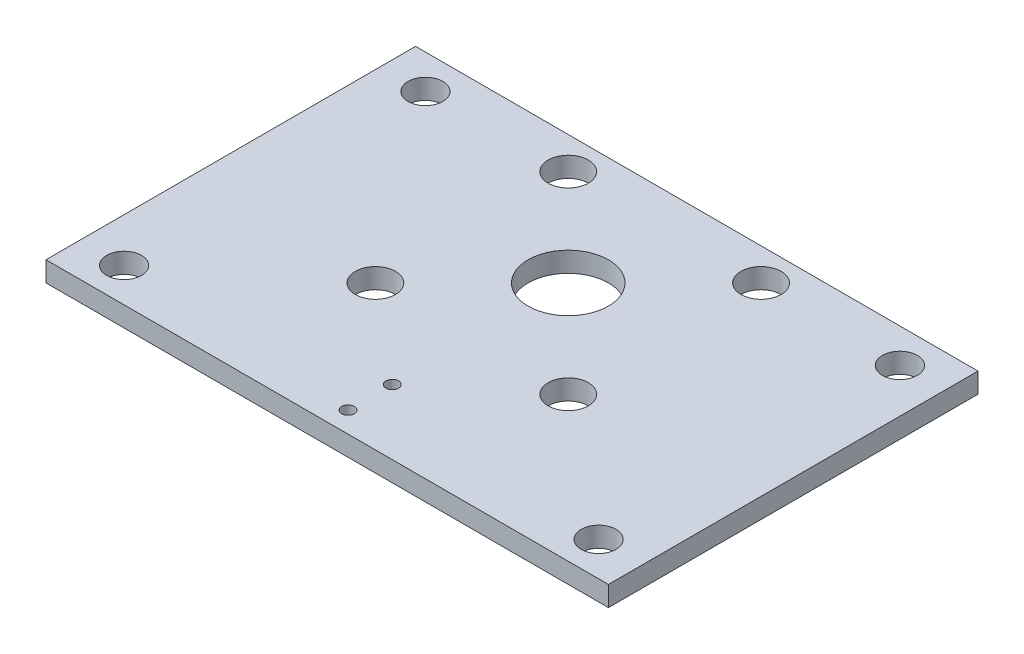
SolidWorks part; units mm, degrees
ref_plane "Front Plane" through (0, 0, 0) normal (0, 0, 1) x (1, 0, 0)
ref_plane "Top Plane" through (0, 0, 0) normal (0, 1, 0) x (1, 0, 0)
ref_plane "Right Plane" through (0, 0, 0) normal (1, 0, 0) x (0, 0, -1)
sketch "Sketch1" plane through (0, 0, 0) normal (0, 1, 0) x (1, 0, 0)
  line L1 (-88.9, 40.64) -> (88.9, 40.64)
  line L2 (-88.9, 40.64) -> (-88.9, -76.2)
  line L4 (88.9, 40.64) -> (88.9, -76.2)
  line L9 (-88.9, -76.2) -> (88.9, -76.2)
  point P0 (0, 0)
  point P10 (0, -76.2)
  dimension "D1" = 116.84
  dimension "D2" = 177.8
  dimension "D4" = 76.2
extrude "Boss-Extrude1" add sketch "Sketch1" along normal mid plane 6.35
hole_wizard "1 (1) Diameter Hole1" positions "Sketch3" profile "Sketch2" hole size "1" standard "ANSI Inch" end condition through all
sketch "Sketch3" plane through (0, 3.175, 0) normal (0, 1, 0) x (1, 0, 0)
  point P0 (0, 0)
sketch "Sketch2" plane through (0, 3.175, 0) normal (1, 0, 0) x (0, 0, 1)
  line L0 (0, 0) -> (0, 6.35)
  line L1 (0, 6.35) -> (12.7, 6.35)
  line L2 (12.7, 6.35) -> (12.7, 0)
  line L5 (12.7, 0) -> (0, 0)
  line L11 (0, -6.35) -> (0, 107.95) construction
  dimension "Thru Hole Dia." = 25.4
  dimension "Thru Hole Depth" = 6.35
hole_wizard "1/2 (0.5) Diameter Hole1" positions "Sketch5" profile "Sketch4" hole size "1/2" standard "ANSI Inch" end condition through all
sketch "Sketch5" plane through (0, 3.175, 0) normal (0, 1, 0) x (1, 0, 0)
  line L1 (-30.48, 30.48) -> (30.48, 30.48)
  line L2 (-30.48, 30.48) -> (-30.48, -30.48)
  line L3 (-30.48, -30.48) -> (30.48, -30.48)
  line L4 (30.48, 30.48) -> (30.48, -30.48)
  line L5 (-30.48, 30.48) -> (30.48, -30.48) construction
  line L6 (-30.48, -30.48) -> (30.48, 30.48) construction
  point P2 (30.48, -30.48)
  point P5 (-30.48, 30.48)
  point P6 (-30.48, -30.48)
  point P7 (30.48, 30.48)
  dimension "D1" = 60.96
sketch "Sketch4" plane through (30.48, 3.175, 30.48) normal (1, 0, 0) x (0, 0, 1)
  line L0 (0, 0) -> (0, 6.35)
  line L1 (0, 6.35) -> (6.35, 6.35)
  line L2 (6.35, 6.35) -> (6.35, 0)
  line L5 (6.35, 0) -> (0, 0)
  line L11 (0, -6.35) -> (0, 107.95) construction
  dimension "Thru Hole Dia." = 12.7
  dimension "Thru Hole Depth" = 6.35
hole_wizard "Ø4.0 (4) Diameter Hole1" positions "Sketch7" profile "Sketch6" hole size "Ø4.0" standard "ANSI Metric" end condition through all
sketch "Sketch7" plane through (0, 3.175, 0) normal (0, 1, 0) x (1, 0, 0)
  point P0 (0, -55.63)
  point P2 (0, -69.63)
  dimension "D1" = 55.63
  dimension "D2" = 14
sketch "Sketch6" plane through (0, 3.175, 55.63) normal (1, 0, 0) x (0, 0, 1)
  line L0 (0, 0) -> (0, 6.35)
  line L1 (0, 6.35) -> (2, 6.35)
  line L2 (2, 6.35) -> (2, 0)
  line L5 (2, 0) -> (0, 0)
  line L11 (0, -6.35) -> (0, 107.95) construction
  dimension "Thru Hole Dia." = 4
  dimension "Thru Hole Depth" = 6.35
hole_wizard "M10 Clearance Hole1" positions "Sketch9" profile "Sketch8" hole size "M10" standard "ANSI Metric" end condition through all
sketch "Sketch9" plane through (0, 3.175, 0) normal (0, 1, 0) x (1, 0, 0)
  line L1 (-75, 29.845) -> (75, 29.845)
  line L2 (-75, 29.845) -> (-75, -65.405)
  line L3 (-75, -65.405) -> (75, -65.405)
  line L4 (75, 29.845) -> (75, -65.405)
  line L5 (88.9, -17.78) -> (-88.9, -17.78) construction
  line L6 (88.9, -76.2) -> (88.9, 40.64) construction
  line L7 (-88.9, 40.64) -> (-88.9, -76.2) construction
  point P2 (75, -65.405)
  point P5 (-75, 29.845)
  point P6 (-75, -65.405)
  point P7 (75, 29.845)
  point P17 (75, -17.78)
  point P18 (0, 29.845)
  dimension "D1" = 95.25
  dimension "D2" = 150
sketch "Sketch8" plane through (75, 3.175, 65.405) normal (1, 0, 0) x (0, 0, 1)
  line L0 (0, 0) -> (0, 6.35)
  line L1 (0, 6.35) -> (5.5, 6.35)
  line L2 (5.5, 6.35) -> (5.5, 0)
  line L5 (5.5, 0) -> (0, 0)
  line L11 (0, -6.35) -> (0, 107.95) construction
  dimension "Thru Hole Dia." = 11
  dimension "Thru Hole Depth" = 6.35
